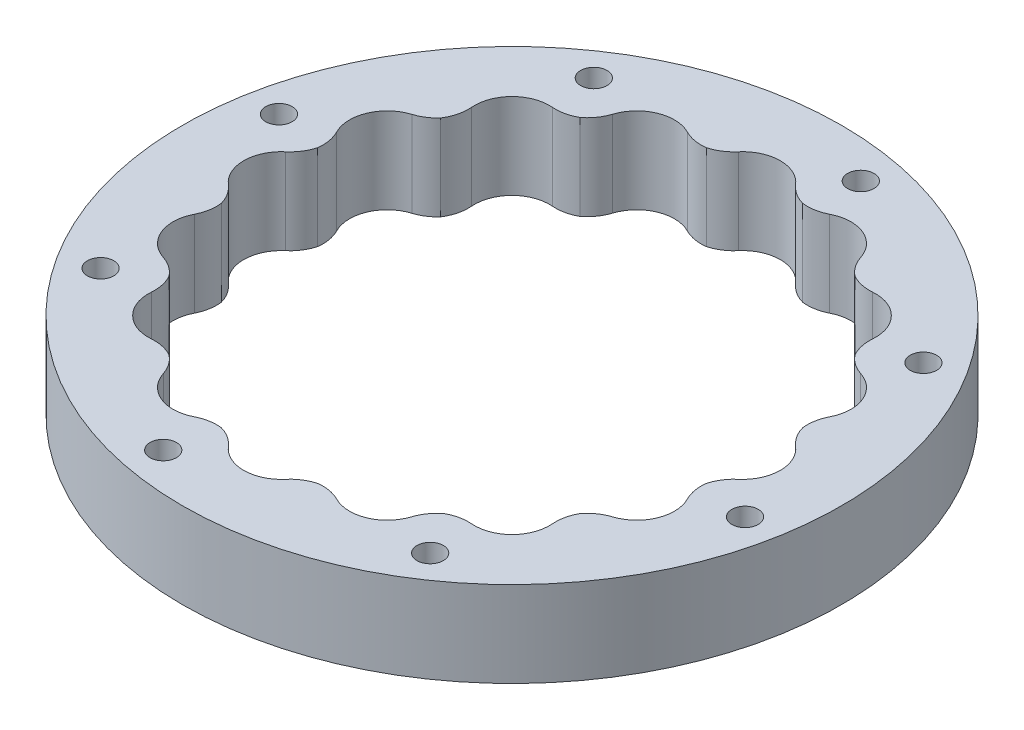
SolidWorks part; units mm, degrees
ref_plane "Front Plane" through (0, 0, 0) normal (0, 0, 1) x (1, 0, 0)
ref_plane "Top Plane" through (0, 0, 0) normal (0, 1, 0) x (1, 0, 0)
ref_plane "Right Plane" through (0, 0, 0) normal (1, 0, 0) x (0, 0, -1)
sketch "Sketch1" plane through (0, 0, 0) normal (0, 1, 0) x (1, 0, 0)
  circle A0 centre (0, 0) radius 35
  circle A1 centre (0, 0) radius 50
  circle A2 centre (0, 0) radius 37.5
  circle A3 centre (0, 35) radius 5.7
  circle A4 centre (13.3939, 32.3358) radius 5.7
  circle A5 centre (24.7487, 24.7487) radius 5.7
  circle A6 centre (32.3358, 13.3939) radius 5.7
  circle A7 centre (35, 0) radius 5.7
  circle A8 centre (32.3358, -13.3939) radius 5.7
  circle A9 centre (24.7487, -24.7487) radius 5.7
  circle A10 centre (13.3939, -32.3358) radius 5.7
  circle A11 centre (0, -35) radius 5.7
  circle A12 centre (-13.3939, -32.3358) radius 5.7
  circle A13 centre (-24.7487, -24.7487) radius 5.7
  circle A14 centre (-32.3358, -13.3939) radius 5.7
  circle A15 centre (-35, 0) radius 5.7
  circle A16 centre (-32.3358, 13.3939) radius 5.7
  circle A17 centre (-24.7487, 24.7487) radius 5.7
  circle A18 centre (-13.3939, 32.3358) radius 5.7
  point P16 (0, 0)
  dimension "D1" = 70
  dimension "D2" = 75
  dimension "D3" = 100
  dimension "D4" = 11.4
  dimension "D5" = 16
extrude "Boss-Extrude1" add sketch "Sketch1" along normal blind 13 contours A1 A18 A2 A3 A4 A5 A6 A7 A8 A9 A10 A11 A12 A13 A14 A15 A16 A17 region at (-48.5858, 0, 0)
fillet "Fillet1" radius 6 31 edges at (-36.3232, 6.5, 9.3208) (-37.1251, 6.5, 5.289) (-37.1251, 6.5, -5.289) (-36.3232, 6.5, -9.3208) (-32.2751, 6.5, 19.0936) (-29.9913, 6.5, 22.5115) (-22.5115, 6.5, 29.9913) (-19.0936, 6.5, 32.2751) (-9.3208, 6.5, 36.3232) (-5.289, 6.5, 37.1251) (5.289, 6.5, 37.1251) (9.3208, 6.5, 36.3232) (19.0936, 6.5, 32.2751) (32.2751, 6.5, 19.0936) (29.9913, 6.5, 22.5115) (22.5115, 6.5, 29.9913) (36.3232, 6.5, 9.3208) (37.1251, 6.5, 5.289) (37.1251, 6.5, -5.289) (36.3232, 6.5, -9.3208) (32.2751, 6.5, -19.0936) (29.9913, 6.5, -22.5115) (22.5115, 6.5, -29.9913) (19.0936, 6.5, -32.2751) (9.3208, 6.5, -36.3232) (5.289, 6.5, -37.1251) (-5.289, 6.5, -37.1251) (-9.3208, 6.5, -36.3232) (-19.0936, 6.5, -32.2751) (-22.5115, 6.5, -29.9913) (-29.9913, 6.5, -22.5115)
fillet "Fillet2" radius 6 1 edges at (-32.2751, 6.5, -19.0936)
sketch "Sketch2" plane through (0, 13, 0) normal (0, 1, 0) x (1, 0, 0)
  line L0 (0, 0) -> (31.1916, 20.8415)
  line L1 (31.1916, 20.8415) -> (37.4161, 25.0007)
  circle A0 centre (0, 0) radius 45
  circle A1 centre (37.4161, 25.0007) radius 2
  dimension "D1" = 90
extrude "Cut-Extrude1" cut sketch "Sketch2" against normal blind 13 contours A1
pattern_circular "CirPattern1" count 8 every 45 about axis through (0, 13, 0) along (0, 1, 0) of "Cut-Extrude1"
equation "\"D_SUN\"=70"
equation "\"D1@Sketch1\"=\"D_SUN\""
equation "\"D_INNER\"=75"
equation "\"D2@Sketch1\"=\"D_INNER\""
equation "\"D_OUTER\"=100"
equation "\"D3@Sketch1\"=\"D_OUTER\""
equation "\"D_BEAR\"= 11.4"
equation "\"D4@Sketch1\"=\"D_BEAR\""
equation "\"G_RATIO\"= 15"
equation "\"D5@Sketch1\"=\"G_RATIO\"+1"
equation "\"D_SCREW\"=90"
equation "\"D1@Sketch2\"= \"D_SCREW\""
equation "\"R_SCREW\"=4"
equation "\"THICK_MID\"= 13"
equation "\"D1@Boss-Extrude1\"=\"THICK_MID\""
equation "\"D2@Sketch2\"=\"R_SCREW\""
equation "\"D1@Cut-Extrude1\"=\"THICK_MID\""
equation "\"D2@CirPattern1\"=360/(8)"
